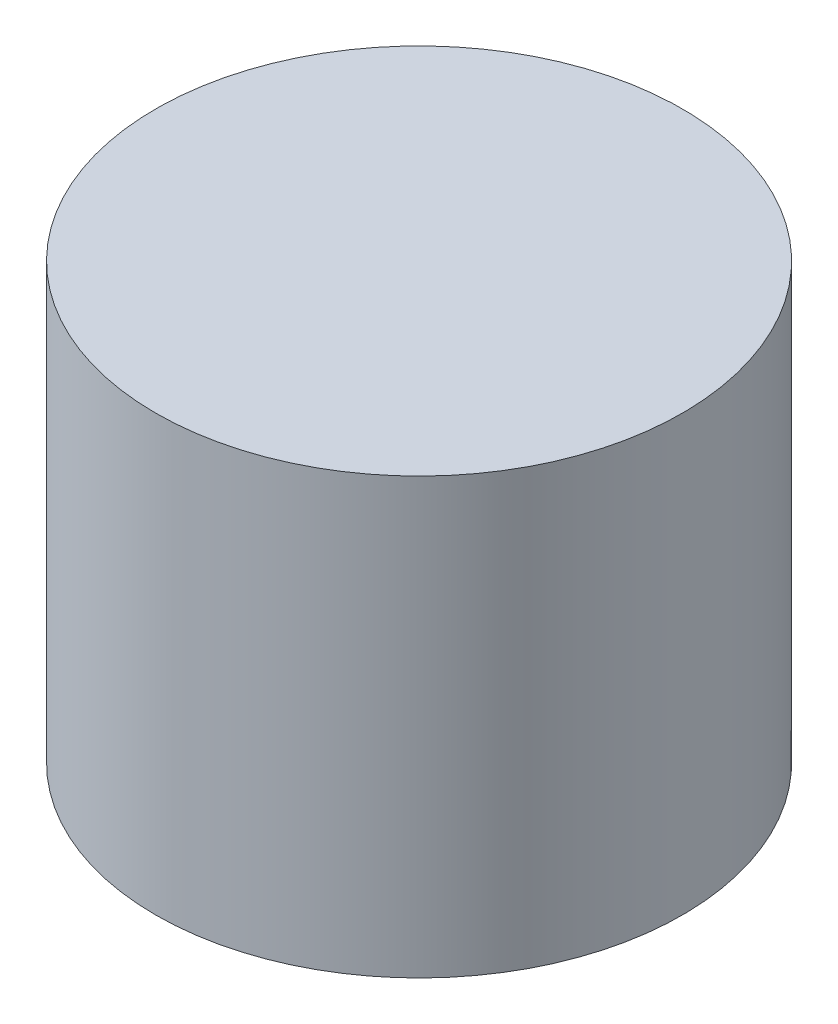
SolidWorks part; units mm, degrees
ref_plane "Front Plane" through (0, 0, 0) normal (0, 0, 1) x (1, 0, 0)
ref_plane "Top Plane" through (0, 0, 0) normal (0, 1, 0) x (1, 0, 0)
ref_plane "Right Plane" through (0, 0, 0) normal (1, 0, 0) x (0, 0, -1)
sketch "Sketch1" plane through (0, 0, 0) normal (0, 1, 0) x (1, 0, 0)
  circle A0 centre (0, 0) radius 32
  dimension "D1" = 64
extrude "Boss-Extrude1" add sketch "Sketch1" along normal mid plane 52.8
